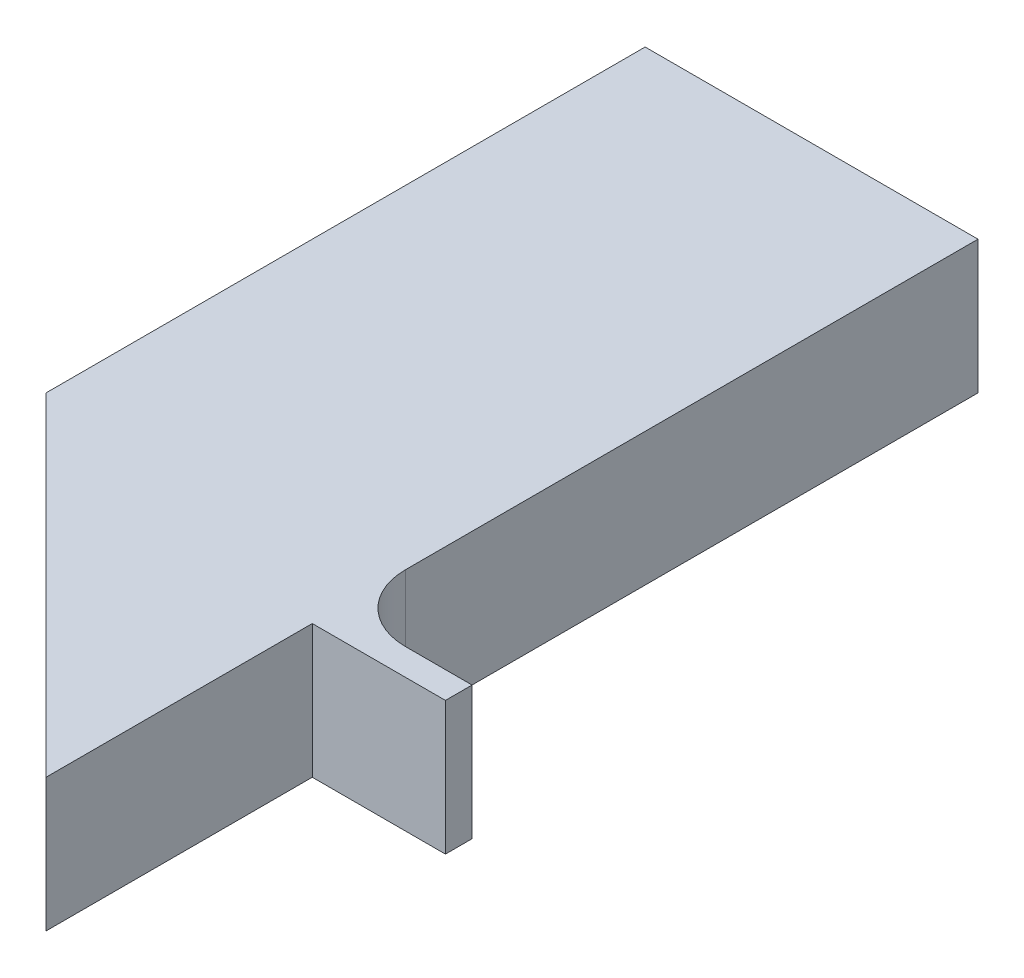
SolidWorks part; units mm, degrees
ref_plane "Front Plane" through (0, 0, 0) normal (0, 0, 1) x (1, 0, 0)
ref_plane "Top Plane" through (0, 0, 0) normal (0, 1, 0) x (1, 0, 0)
ref_plane "Right Plane" through (0, 0, 0) normal (1, 0, 0) x (0, 0, -1)
sketch "Sketch1" plane through (0, 0, 0) normal (0, 1, 0) x (1, 0, 0)
  line L0 (-50, 50) -> (0, 0)
  line L1 (-50, 140) -> (0, 140)
  line L2 (-50, 140) -> (-50, 50)
  line L4 (0, 140) -> (0, 0)
  dimension "D1" = 50
  dimension "D2" = 45
  dimension "D3" = 140
extrude "Boss-Extrude1" add sketch "Sketch1" along normal blind 20
sketch "Sketch2" plane through (0, 0, 0) normal (1, 0, 0) x (0, 0, -1)
  line L0 (0, 20) -> (140, 20) construction
  line L1 (40, 20) -> (44, 20)
  line L2 (40, 20) -> (40, 0)
  line L3 (40, 0) -> (44, 0)
  line L4 (44, 20) -> (44, 0)
  line L5 (0, 0) -> (140, 0) construction
  line L6 (0, 20) -> (0, 0) construction
  dimension "D1" = 40
  dimension "D2" = 4
extrude "Boss-Extrude2" add sketch "Sketch2" along normal blind 20
sketch "Sketch3" plane through (-50, 0, 0) normal (-1, 0, 0) x (0, 0, 1)
  line L0 (0, 20) -> (0, 0) construction
  line L1 (-46, 16) -> (0, 16)
  line L2 (-46, 16) -> (-46, 4)
  line L3 (-46, 4) -> (0, 4)
  line L4 (0, 16) -> (0, 4)
  line L5 (-50, 20) -> (0, 20) construction
  line L6 (-50, 0) -> (0, 0) construction
  line L7 (-50, 20) -> (-50, 0) construction
  dimension "D1" = 4
  dimension "D2" = 4
  dimension "D3" = 4
extrude "Cut-Extrude1" cut sketch "Sketch3" against normal offset from surface (46 mm away) 4 up to face at (0, 10, -20)
sketch "Sketch4" plane through (0, 0, 0) normal (0, -1, 0) x (1, 0, 0)
  line L0 (-36, -140) -> (-36, -36) construction
  line L3 (20, -44) -> (0, -44) construction
  line L4 (0, -140) -> (-50, -140) construction
  line L5 (-50, -50) -> (0, 0) construction
  line L6 (-50, -140) -> (-50, -50) construction
  circle A0 centre (-36, -59) radius 11
  circle A1 centre (-36, -119) radius 11
  dimension "D1" = 22
  dimension "D2" = 22
  dimension "D3" = 15
  dimension "D4" = 60
  dimension "D5" = 14
extrude "Cut-Extrude2" cut sketch "Sketch4" against normal blind 8
fillet "Fillet1" radius 10 1 edges at (0, 10, -44)
